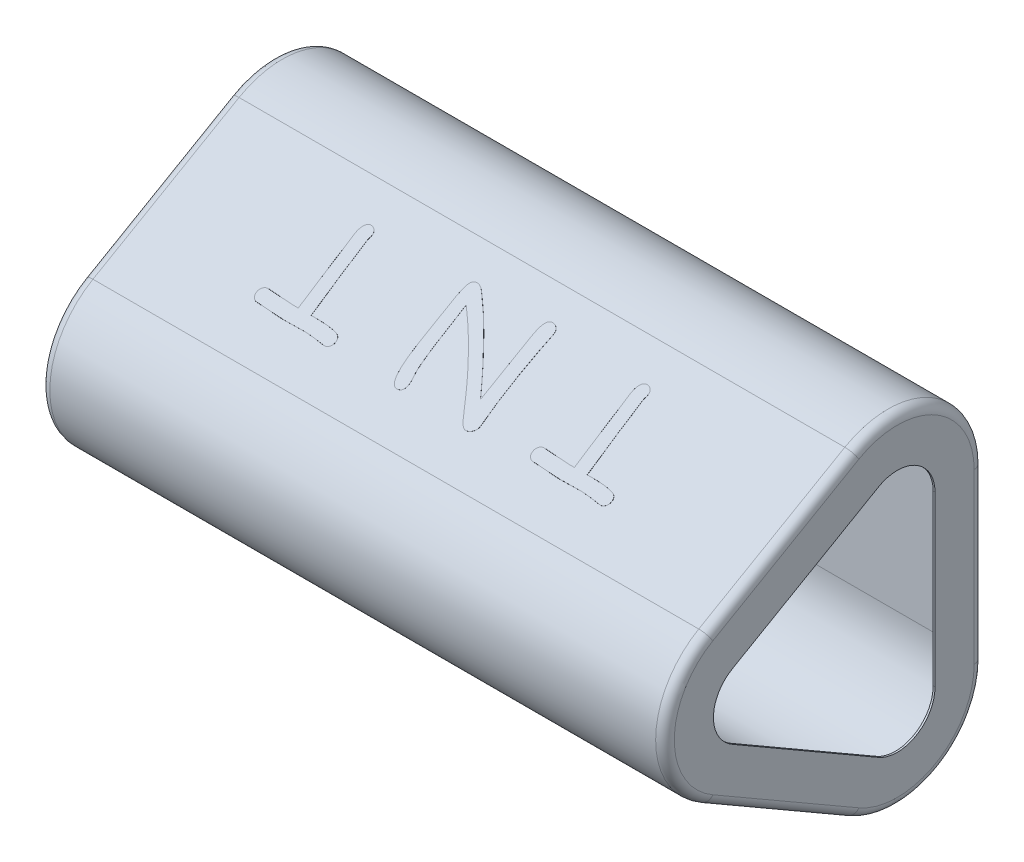
SolidWorks part; units mm, degrees
ref_plane "Front Plane" through (0, 0, 0) normal (1, 0, 0) x (0, 1, 0)
ref_plane "Top Plane" through (0, 0, 0) normal (0, 0, 1) x (0, 1, 0)
ref_plane "Right Plane" through (0, 0, 0) normal (0, 1, 0) x (-1, 0, 0)
sketch "Sketch1" plane through (0, 0, 0) normal (1, 0, 0) x (0, 1, 0)
  line L0 (-7.8375, 29.2501) -> (-16.8875, 13.575)
  line L1 (7.8375, 29.2501) -> (16.8875, 13.575)
  line L2 (-9.05, 0) -> (9.05, 0)
  arc A0 (7.8375, 29.2501) -> (-7.8375, 29.2501) centre (0, 24.7251) ccw
  arc A1 (9.05, 0) -> (16.8875, 13.575) centre (9.05, 9.05) ccw
  arc A2 (-16.8875, 13.575) -> (-9.05, 0) centre (-9.05, 9.05) ccw
  dimension "D1" = 9.05
extrude "Extrude-Thin1" add sketch "Sketch1" along normal blind 67 thin thin type one direction wall 0.2
ref_plane "Plane1" through (33.5, 0, 0) normal (-1, 0, 0) x (0, 0, 1)
extrude "Extrude-Thin2" add sketch "Sketch1<4>" along normal blind 0.2 thin thin type one direction reverse wall 5
sketch "Sketch1<4>" plane through (0, 0, 0) normal (1, 0, 0) x (0, 1, 0) same geometry as "Sketch1"
mirror "Mirror" about plane through (33.5, 0, 0) normal (-1, 0, 0) of "Extrude-Thin2"
fillet "Fillet1" radius 1 24 edges at (0.2, -12.3625, 21.4125) (0.2, 0, 33.7751) (0.2, 12.3625, 21.4125) (0.2, 16.8875, 4.525) (0.2, 0, 0) (0, 12.5357, 21.5125) (0, 17.0607, 4.425) (0, 0, -0.2) (0, -17.0607, 4.425) (0, -12.5357, 21.5125) (0.2, -16.8875, 4.525) (0, 0, 33.9751) (67, -12.5357, 21.5125) (67, 0, 33.9751) (67, 12.5357, 21.5125) (67, 17.0607, 4.425) (67, 0, -0.2) (66.8, -12.3625, 21.4125) (66.8, 0, 33.7751) (66.8, 12.3625, 21.4125) (66.8, 16.8875, 4.525) (66.8, 0, 0) (67, -17.0607, 4.425) (66.8, -16.8875, 4.525)
sketch "Sketch2" plane through (0, 18.717, 10.8063) normal (0, 0.866, 0.5) x (-1, 0, 0)
  line L0 (-66, 6.8125) -> (-1, 6.8125) construction
  line L1 (-66, 21.4125) -> (-66, 3.3125) construction
  line L2 (-1, 3.3125) -> (-1, 21.4125) construction
  line L3 (-66, 3.3125) -> (-1, 3.3125) construction
  text T0 "TNT" font "Comic Sans MS" height 10
  dimension "D1" = 3.5
extrude "Boss-Extrude1" add sketch "Sketch2" along normal blind 0.01
